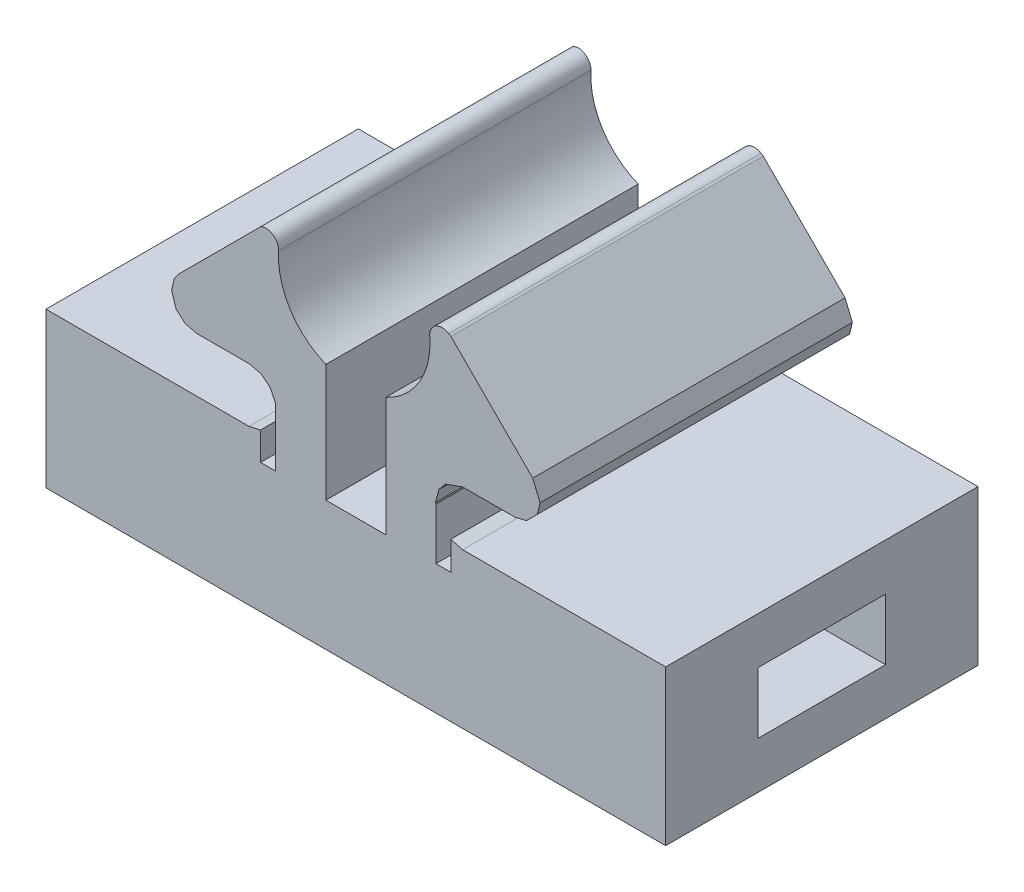
SolidWorks part; units mm, degrees
ref_plane "Front Plane" through (0, 0, 0) normal (0, 0, 1) x (1, 0, 0)
ref_plane "Top Plane" through (0, 0, 0) normal (0, 1, 0) x (1, 0, 0)
ref_plane "Right Plane" through (0, 0, 0) normal (1, 0, 0) x (0, 0, -1)
sketch "Sketch5" plane through (0, 0, 0) normal (0, 0, 1) x (1, 0, 0)
  line L0 (-6.4748, -10.4902) -> (-6.9383, -10.3783)
  line L1 (-6.9383, -10.3783) -> (-7.3088, -10.0545)
  line L2 (-7.3088, -10.0545) -> (-7.4908, -9.4742)
  line L3 (-7.4908, -9.4742) -> (-7.3789, -9.0107)
  line L4 (-7.3789, -9.0107) -> (-7.1932, -8.7558)
  line L5 (-7.1932, -8.7558) -> (-3.8632, -5.4257)
  line L6 (-3.8632, -5.4257) -> (-2.8331, -4.7375)
  line L7 (-2.8331, -4.7375) -> (-1.6181, -4.4958)
  line L8 (-1.6181, -4.4958) -> (1.6181, -4.4958)
  line L9 (1.6181, -4.4958) -> (2.6682, -4.6745)
  line L10 (2.6682, -4.6745) -> (3.8632, -5.4257)
  line L11 (3.8632, -5.4257) -> (7.1932, -8.7558)
  line L12 (7.1932, -8.7558) -> (7.4908, -9.4742)
  line L13 (7.4908, -9.4742) -> (7.3789, -9.9377)
  line L14 (6.4748, -10.4902) -> (6.9383, -10.3783)
  line L15 (6.9383, -10.3783) -> (7.3789, -9.9377)
  line L16 (6.4748, -10.4902) -> (4.3434, -10.4902)
  line L19 (-6.4748, -10.4902) -> (-4.3434, -10.4902)
  line L20 (-4.3434, -10.4902) -> (-3.8632, -10.6)
  line L21 (-3.8632, -10.6) -> (-3.486, -10.8982)
  line L22 (-3.486, -10.8982) -> (-3.2711, -11.3288)
  line L23 (-3.2711, -11.3288) -> (-3.2711, -11.8614)
  line L24 (-3.2711, -11.8614) -> (-3.486, -12.292)
  line L25 (-3.486, -12.292) -> (-3.8632, -12.5902)
  line L26 (-3.8632, -12.5902) -> (-4.3434, -12.7)
  line L27 (-4.3434, -12.7) -> (-9.5504, -12.7)
  line L28 (-9.5504, -12.7) -> (-9.5504, -18.9956)
  line L29 (-9.5504, -18.9956) -> (10.5918, -18.9956)
  line L30 (10.5918, -18.9956) -> (10.5918, -12.7)
  line L31 (10.5918, -12.7) -> (4.3434, -12.7)
  line L32 (4.3434, -12.7) -> (3.8076, -12.5614)
  line L33 (3.8076, -12.5614) -> (3.486, -12.292)
  line L34 (3.486, -12.292) -> (3.2385, -11.5951)
  line L35 (3.2385, -11.5951) -> (3.3771, -11.0593)
  line L36 (3.3771, -11.0593) -> (3.6465, -10.7377)
  line L37 (3.6465, -10.7377) -> (4.3434, -10.4902)
extrude "Boss-Extrude1" add sketch "Sketch5" against normal blind 12.7
sketch "Sketch10" plane through (0, 0, 0) normal (0, 0, 1) x (1, 0, 0)
  circle A0 centre (-0.0665, -6.096) radius 3.0821
extrude "Cut-Extrude1" cut sketch "Sketch10" against normal through all
sketch "Sketch11" plane through (0, 0, 0) normal (0, 0, 1) x (1, 0, 0)
  line L1 (-1.2179, -5.8277) -> (1.2179, -5.8277)
  line L2 (-1.2179, -5.8277) -> (-1.2179, -13.7361)
  line L3 (-1.2179, -13.7361) -> (1.2179, -13.7361)
  line L4 (1.2179, -5.8277) -> (1.2179, -13.7361)
  line L5 (-1.2179, -5.8277) -> (1.2179, -13.7361) construction
  line L6 (-1.2179, -13.7361) -> (1.2179, -5.8277) construction
  point P0 (0, -9.7819)
extrude "Cut-Extrude2" cut sketch "Sketch11" against normal through all
sketch "Sketch13" plane through (-9.5504, 0, 0) normal (-1, 0, 0) x (0, 0, 1)
  line L1 (-8.941, -14.6031) -> (-3.759, -14.6031)
  line L2 (-8.941, -14.6031) -> (-8.941, -17.0925)
  line L3 (-8.941, -17.0925) -> (-3.759, -17.0925)
  line L4 (-3.759, -14.6031) -> (-3.759, -17.0925)
  line L5 (-8.941, -14.6031) -> (-3.759, -17.0925) construction
  line L6 (-8.941, -17.0925) -> (-3.759, -14.6031) construction
  point P0 (-6.35, -15.8478)
extrude "Cut-Extrude4" cut sketch "Sketch13" against normal through all both and the other way through all
fillet "Fillet3" radius 0.508 2 edges at (2.6682, -4.6745, -6.35) (-2.8331, -4.7375, -6.35)
sketch "Sketch17" plane through (0, 0, 0) normal (0, 0, 1) x (1, 0, 0)
  line L0 (3.486, -12.292) -> (3.2385, -11.5951) construction
  line L1 (3.2547, -11.6407) -> (3.8597, -11.6407)
  line L2 (3.2547, -11.6407) -> (3.2547, -13.7361)
  line L3 (3.2547, -13.7361) -> (3.8597, -13.7361)
  line L4 (3.8597, -11.6407) -> (3.8597, -13.7361)
  line L5 (-3.2711, -11.3288) -> (-3.2711, -11.8614) construction
  line L6 (-3.2711, -11.5951) -> (-3.8755, -11.5951)
  line L7 (-3.2711, -11.5951) -> (-3.2711, -13.7361)
  line L8 (-3.2711, -13.7361) -> (-3.8755, -13.7361)
  line L9 (-3.8755, -11.5951) -> (-3.8755, -13.7361)
extrude "Cut-Extrude7" cut sketch "Sketch17" against normal through all
sketch "Sketch19" plane through (-9.5504, 0, 0) normal (-1, 0, 0) x (0, 0, 1)
  line L1 (0, -12.7) -> (-12.7, -12.7)
  line L2 (0, -12.7) -> (0, -18.9956)
  line L3 (0, -18.9956) -> (-12.7, -18.9956)
  line L4 (-12.7, -12.7) -> (-12.7, -18.9956)
extrude "Boss-Extrude2" add sketch "Sketch19" along normal blind 3.048
sketch "Sketch20" plane through (10.5918, 0, 0) normal (1, 0, 0) x (0, 0, -1)
  line L1 (0, -12.7) -> (12.7, -12.7)
  line L2 (0, -12.7) -> (0, -18.9956)
  line L3 (0, -18.9956) -> (12.7, -18.9956)
  line L4 (12.7, -12.7) -> (12.7, -18.9956)
  point P6 (9.1257, -17.9008)
extrude "Boss-Extrude3" add sketch "Sketch20" along normal blind 2.0066
sketch "Sketch22" plane through (-12.5984, 0, 0) normal (-1, 0, 0) x (0, 0, 1)
  line L1 (-8.941, -14.6031) -> (-3.759, -14.6031)
  line L2 (-8.941, -14.6031) -> (-8.941, -17.0925)
  line L3 (-8.941, -17.0925) -> (-3.759, -17.0925)
  line L4 (-3.759, -14.6031) -> (-3.759, -17.0925)
extrude "Cut-Extrude8" cut sketch "Sketch22" against normal through all
